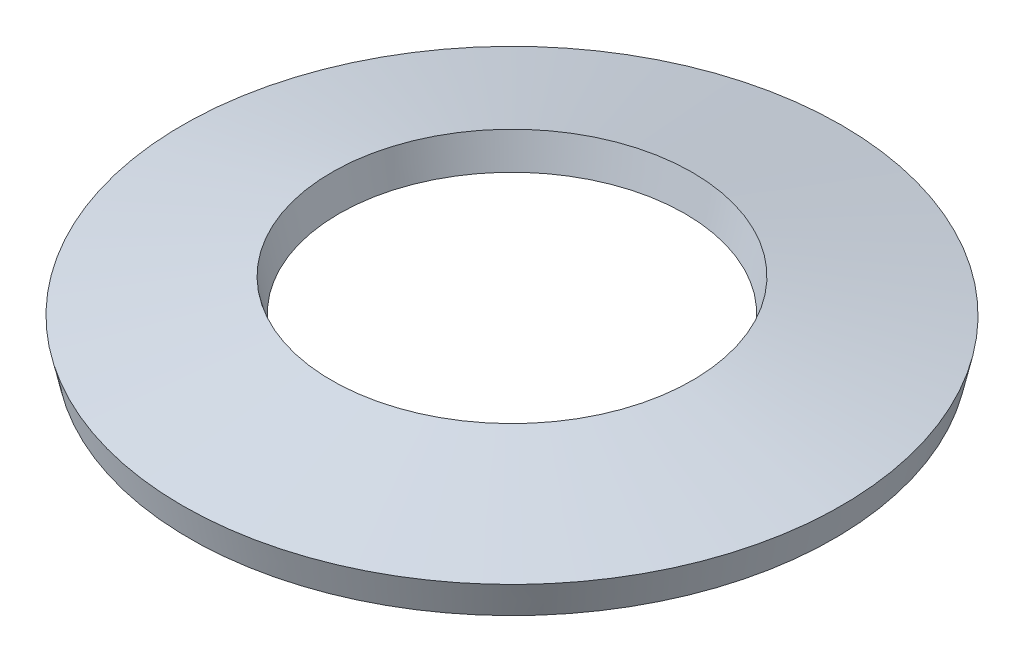
SolidWorks part; units mm, degrees
ref_plane "Front" through (0, 0, 0) normal (0, 0, 1) x (1, 0, 0)
ref_plane "Top" through (0, 0, 0) normal (0, 1, 0) x (1, 0, 0)
ref_plane "Right" through (0, 0, 0) normal (1, 0, 0) x (0, 0, -1)
sketch "Sketch1" plane through (0, 0, 0) normal (0, 0, 1) x (1, 0, 0)
  line L0 (3.9117, 0) -> (2.1, 0.4099)
  line L1 (2.1, 0.4099) -> (2.1883, 0.8)
  line L2 (2.1883, 0.8) -> (4, 0.3901)
  line L3 (4, 0.3901) -> (3.9117, 0)
  line L4 (0, 0) -> (0, 0.8) construction
  line L5 (-4, 0.3901) -> (-3.9117, 0) construction
  line L6 (-2.1883, 0.8) -> (-4, 0.3901) construction
  line L7 (-2.1, 0.4099) -> (-2.1883, 0.8) construction
  line L8 (-3.9117, 0) -> (-2.1, 0.4099) construction
  point P5 (2.1441, 0.6049)
  point P8 (-2.1441, 0.6049)
  dimension "D1" = 1.8575
  dimension "ID" = 4.2
  dimension "OD" = 8
  dimension "Thickness" = 0.4
  dimension "Height" = 0.8
revolve "Revolve1" add sketch "Sketch1" angle 360 about L4
sketch "Sketch15" plane through (0, 0, 0) normal (0, 1, 0) x (1, 0, 0)
  circle A0 centre (0, 0) radius 4
  circle A1 centre (0, 0) radius 2.1
ref_plane "Contact Plane 1" through (0, 0, 0) normal (0, 1, 0) x (-1, 0, 0)
ref_plane "Contact Plane 2" through (0, 0.8, 0) normal (0, 1, 0) x (-1, 0, 0)
ref_axis "Center Axis 1" through (0, 0, 0) along (0, 1, 0)
